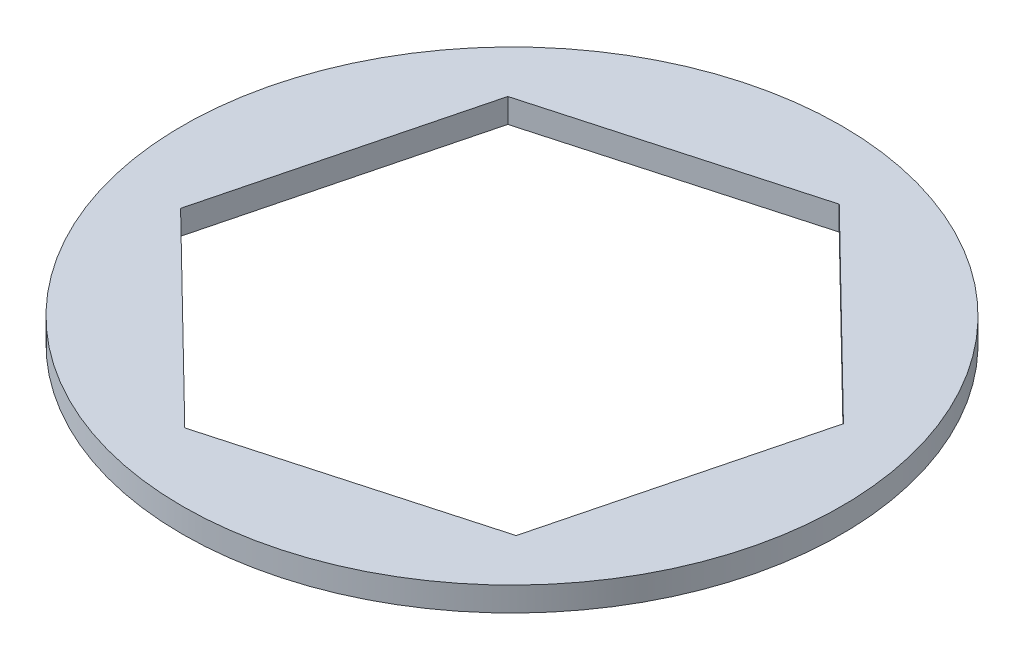
SolidWorks part; units mm, degrees
ref_plane "Front Plane" through (0, 0, 0) normal (0, 0, 1) x (1, 0, 0)
ref_plane "Top Plane" through (0, 0, 0) normal (0, 1, 0) x (1, 0, 0)
ref_plane "Right Plane" through (0, 0, 0) normal (1, 0, 0) x (0, 0, -1)
sketch "Sketch1" plane through (0, 0, 0) normal (0, 1, 0) x (1, 0, 0)
  line L1 (1.9289, 7.5291) -> (-5.5559, 5.4351)
  line L2 (-5.5559, 5.4351) -> (-7.4849, -2.094)
  line L3 (-7.4849, -2.094) -> (-1.9289, -7.5291)
  line L4 (-1.9289, -7.5291) -> (5.5559, -5.4351)
  line L5 (5.5559, -5.4351) -> (7.4849, 2.094)
  line L6 (7.4849, 2.094) -> (1.9289, 7.5291)
  circle A0 centre (0, 0) radius 9.525
  circle A1 centre (0, 0) radius 6.731 construction
  dimension "D1" = 19.05
  dimension "D2" = 13.462
extrude "Boss-Extrude1" add sketch "Sketch1" along normal blind 0.7
